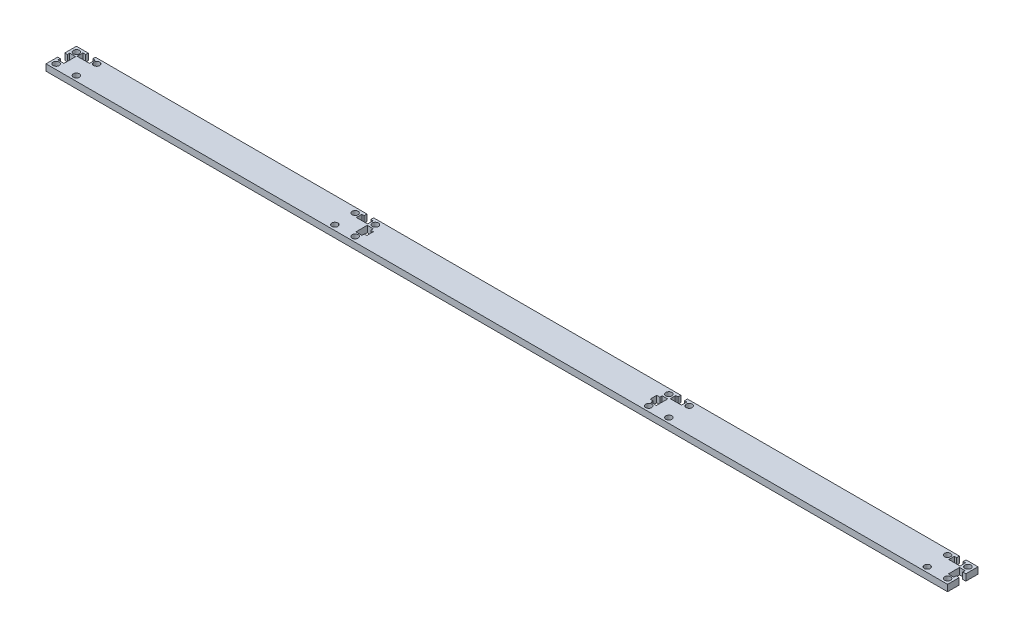
SolidWorks part; units mm, degrees
ref_plane "Front Plane" through (0, 0, 0) normal (0, 0, 1) x (1, 0, 0)
ref_plane "Top Plane" through (0, 0, 0) normal (0, 1, 0) x (1, 0, 0)
ref_plane "Right Plane" through (0, 0, 0) normal (1, 0, 0) x (0, 0, -1)
sketch "Sketch1" plane through (0, 0, 0) normal (0, 1, 0) x (1, 0, 0)
  line L0 (152.4, 7.5) -> (144.9, 7.5)
  line L1 (0, 0) -> (152.4, 0)
  line L2 (0, 0) -> (0, 15)
  line L3 (0, 15) -> (152.4, 15)
  line L4 (152.4, 0) -> (152.4, 15)
  line L5 (0, 7.5) -> (7.5, 7.5)
  line L6 (7.5, 7.5) -> (7.5, 12.5)
  line L7 (7.5, 12.5) -> (2.5, 12.5)
  line L8 (7.5, 12.5) -> (12.5, 12.5)
  line L9 (7.5, 7.5) -> (7.5, 2.5)
  line L10 (7.5, 2.5) -> (2.5, 2.5)
  line L11 (7.5, 2.5) -> (12.5, 2.5)
  line L12 (76.2, 0) -> (76.2, 15)
  line L13 (152.4, 0) -> (152.4, 15)
  line L14 (152.4, 0) -> (292.1, 0)
  line L15 (152.4, 15) -> (292.1, 15)
  line L16 (222.25, 0) -> (222.25, 15)
  line L17 (292.1, 0) -> (292.1, 15)
  line L18 (444.5, 15) -> (292.1, 15)
  line L19 (292.1, 0) -> (292.1, 15)
  line L20 (444.5, 0) -> (292.1, 0)
  line L21 (444.5, 0) -> (444.5, 15)
  circle A0 centre (2.5, 2.5) radius 1.5
  circle A1 centre (2.5, 12.5) radius 1.5
  circle A2 centre (12.5, 12.5) radius 1.5
  circle A3 centre (12.5, 2.5) radius 1.5
  circle A4 centre (149.9, 12.5) radius 1.5
  circle A5 centre (139.9, 12.5) radius 1.5
  circle A6 centre (149.9, 2.5) radius 1.5
  circle A7 centre (139.9, 2.5) radius 1.5
  circle A8 centre (432, 12.5) radius 1.5
  circle A9 centre (442, 12.5) radius 1.5
  circle A10 centre (442, 2.5) radius 1.5
  circle A11 centre (432, 2.5) radius 1.5
  circle A12 centre (294.6, 12.5) radius 1.5
  circle A13 centre (304.6, 12.5) radius 1.5
  circle A14 centre (304.6, 2.5) radius 1.5
  circle A15 centre (294.6, 2.5) radius 1.5
  dimension "D11" = 69.85
  dimension "D1" = 15
  dimension "D2" = 152.4
  dimension "D3" = 7.5
  dimension "D4" = 7.5
  dimension "D5" = 5
  dimension "D6" = 5
  dimension "D7" = 5
  dimension "D8" = 5
  dimension "D9" = 5
  dimension "D10" = 5
extrude "Boss-Extrude1" add sketch "Sketch1" along normal blind 3.175 contours A3 A0 L2 L1 L12 L3 A1 A2 | L12 L1 L4 L3 A6 A4 A5 A7 | L14 L16 L15 L4 | L14 L17 L15 L16 | L20 L21 L18 L17 A15 A14 A13 A12 A10 A8 A9 A11 region at (38.8762, 0, -7.5) region at (113.5238, 0, -7.5) region at (187.325, 0, -7.5) region at (257.175, 0, -7.5) region at (368.3, 0, -7.5)
sketch "Sketch4" plane through (0, 3.175, 0) normal (0, 1, 0) x (1, 0, 0)
  line L0 (444.5, 7.5) -> (432.4339, 7.5)
  line L1 (444.5, 0) -> (444.5, 15) construction
  line L2 (0, 15) -> (444.5, 15) construction
  line L3 (222.25, 15) -> (222.25, 0)
  line L4 (0, 0) -> (444.5, 0) construction
  line L5 (444.5, 9) -> (442.2, 9)
  line L6 (442.2, 9) -> (442.2, 10.15)
  line L7 (442.2, 10.15) -> (440.5, 10.15)
  line L8 (440.5, 10.15) -> (440.5, 7.5)
  line L9 (444.5, 9.25) -> (442.45, 9.25)
  line L10 (442.45, 9.25) -> (442.45, 10.4)
  line L11 (442.45, 10.4) -> (440.25, 10.4)
  line L12 (440.25, 10.4) -> (440.25, 7.5)
  line L13 (444.5, 5.75) -> (442.45, 5.75)
  line L14 (442.45, 5.75) -> (442.45, 4.6)
  line L15 (442.45, 4.6) -> (440.25, 4.6)
  line L16 (440.25, 4.6) -> (440.25, 7.5)
  line L17 (0, 9.25) -> (2.05, 9.25)
  line L18 (2.05, 9.25) -> (2.05, 10.4)
  line L19 (0, 5.75) -> (2.05, 5.75)
  line L20 (2.05, 5.75) -> (2.05, 4.6)
  line L21 (2.05, 4.6) -> (4.25, 4.6)
  line L22 (4.25, 4.6) -> (4.25, 7.5)
  line L23 (4.25, 10.4) -> (4.25, 7.5)
  line L24 (2.05, 10.4) -> (4.25, 10.4)
  line L25 (0, 9.25) -> (0, 5.75)
  line L26 (444.5, 9.25) -> (444.5, 5.75)
  line M20 (0, 15) -> (0, 0)
  line M22 (444.5, 0) -> (444.5, 15)
  dimension "D1" = 1.5
  dimension "D2" = 1.15
  dimension "D3" = 1.7
  dimension "D4" = 2.65
  dimension "D5" = 2.3
  dimension "D6" = 0.25
extrude "Cut-Extrude2" cut sketch "Sketch4" against normal blind 10 contours L16 L15 L14 L13 L0 M22 | L7 L8 L0 L5 L6 M22 | L24 L18 L17 L19 L20 L21 L22 L23 M20 region at (442.1148, 3.175, -6.257) region at (442.2174, 3.175, -8.5756) region at (2.3852, 3.175, -7.5)
sketch "Sketch6" plane through (440.5, 0, 0) normal (1, 0, 0) x (0, 0, -1)
  line L0 (10.15, 0) -> (7.5, 0) construction
  line L5 (7.5, 3.175) -> (10.15, 3.175)
  line L6 (7.5, 3.175) -> (7.5, 0)
  line L7 (7.5, 0) -> (10.15, 0)
  line L8 (10.15, 3.175) -> (10.15, 0)
extrude "Cut-Extrude3" cut sketch "Sketch6" against normal blind 0.25
sketch "Sketch7" plane through (0, 3.175, 0) normal (0, 1, 0) x (1, 0, 0)
  line L0 (440.25, 4.6) -> (440.25, 10.15)
  line L1 (440.25, 10.15) -> (442.2, 10.15)
  line L2 (442.2, 10.15) -> (442.2, 9)
  line L3 (442.2, 9) -> (444.5, 9)
  line L4 (444.5, 9) -> (444.5, 5.75)
  line L5 (444.5, 5.75) -> (442.45, 5.75)
  line L6 (444.5, 5.75) -> (442.45, 5.75) construction
  line L7 (442.45, 5.75) -> (442.45, 4.6)
  line L8 (442.45, 5.75) -> (442.45, 4.6) construction
  line L9 (442.45, 4.6) -> (440.25, 4.6) construction
  line L10 (442.45, 4.6) -> (440.25, 4.6)
  line L11 (368.3, 15) -> (368.3, 0)
  line L12 (0, 15) -> (444.5, 15) construction
  line L13 (0, 0) -> (444.5, 0) construction
  line L30 (439.75, 13.1) -> (439.75, 10.9)
  line L31 (439.75, 10.9) -> (434.2, 10.9)
  line L32 (434.2, 10.9) -> (434.2, 12.85)
  line L33 (434.2, 12.85) -> (435.35, 12.85)
  line L34 (435.35, 12.85) -> (435.35, 15.15)
  line L35 (435.35, 15.15) -> (438.6, 15.15)
  line L36 (438.6, 15.15) -> (438.6, 13.1)
  line L37 (438.6, 13.1) -> (439.75, 13.1)
  line L38 (431.25, 10.4) -> (433.45, 10.4) [skipped]
  line L39 (433.45, 10.4) -> (433.45, 4.85) [skipped]
  line L40 (433.45, 4.85) -> (431.5, 4.85) [skipped]
  line L41 (431.5, 4.85) -> (431.5, 6) [skipped]
  line L42 (431.5, 6) -> (429.2, 6) [skipped]
  line L43 (429.2, 6) -> (429.2, 9.25) [skipped]
  line L44 (429.2, 9.25) -> (431.25, 9.25) [skipped]
  line L45 (431.25, 9.25) -> (431.25, 10.4) [skipped]
  line L46 (433.95, 1.9) -> (433.95, 4.1) [skipped]
  line L47 (433.95, 4.1) -> (439.5, 4.1) [skipped]
  line L48 (439.5, 4.1) -> (439.5, 2.15) [skipped]
  line L49 (439.5, 2.15) -> (438.35, 2.15) [skipped]
  line L50 (438.35, 2.15) -> (438.35, -0.15) [skipped]
  line L51 (438.35, -0.15) -> (435.1, -0.15) [skipped]
  line L52 (435.1, -0.15) -> (435.1, 1.9) [skipped]
  line L53 (435.1, 1.9) -> (433.95, 1.9) [skipped]
  line L54 (298, 13.1) -> (296.85, 13.1)
  line L55 (298, 15.15) -> (298, 13.1)
  line L56 (301.25, 15.15) -> (298, 15.15)
  line L57 (301.25, 12.85) -> (301.25, 15.15)
  line L58 (302.4, 12.85) -> (301.25, 12.85)
  line L59 (302.4, 10.9) -> (302.4, 12.85)
  line L60 (296.85, 10.9) -> (302.4, 10.9)
  line L61 (296.85, 13.1) -> (296.85, 10.9)
  line L62 (294.15, 4.6) -> (296.35, 4.6)
  line L63 (294.15, 5.75) -> (294.15, 4.6)
  line L64 (292.1, 5.75) -> (294.15, 5.75)
  line L65 (292.1, 9) -> (292.1, 5.75)
  line L66 (294.4, 9) -> (292.1, 9)
  line L67 (294.4, 10.15) -> (294.4, 9)
  line L68 (296.35, 10.15) -> (294.4, 10.15)
  line L69 (296.35, 4.6) -> (296.35, 10.15)
  line L70 (222.25, 15) -> (222.25, -3.2604)
  line L71 (148.15, 4.6) -> (148.15, 10.15)
  line L72 (148.15, 10.15) -> (150.1, 10.15)
  line L73 (150.1, 10.15) -> (150.1, 9)
  line L74 (150.1, 9) -> (152.4, 9)
  line L75 (152.4, 9) -> (152.4, 5.75)
  line L76 (152.4, 5.75) -> (150.35, 5.75)
  line L77 (150.35, 5.75) -> (150.35, 4.6)
  line L78 (150.35, 4.6) -> (148.15, 4.6)
  line L79 (147.65, 13.1) -> (147.65, 10.9)
  line L80 (147.65, 10.9) -> (142.1, 10.9)
  line L81 (142.1, 10.9) -> (142.1, 12.85)
  line L82 (142.1, 12.85) -> (143.25, 12.85)
  line L83 (143.25, 12.85) -> (143.25, 15.15)
  line L84 (143.25, 15.15) -> (146.5, 15.15)
  line L85 (146.5, 15.15) -> (146.5, 13.1)
  line L86 (146.5, 13.1) -> (147.65, 13.1)
  circle A0 centre (294.6, 12.5) radius 1.5 construction
  line M51 (440.25, 4.6) -> (440.25, 10.15)
  line M52 (440.25, 10.15) -> (442.2, 10.15)
  line M53 (442.2, 10.15) -> (442.2, 9)
  line M54 (442.2, 9) -> (444.5, 9)
  line M56 (444.5, 15) -> (0, 15)
  line M68 (444.5, 5.75) -> (442.45, 5.75)
  line M69 (442.45, 5.75) -> (442.45, 4.6)
  line M70 (442.45, 4.6) -> (440.25, 4.6)
  dimension "D1" = 73.7
  dimension "D2" = 4
extrude "Cut-Extrude4" cut sketch "Sketch7" against normal blind 10 contours L78 L77 L76 L75 L74 L73 L72 L71 | L86 L85 L83 L82 L81 L80 L79 M56 | L62 L69 L68 L67 L66 L65 L64 L63 | L54 L61 L60 L59 L58 L57 L55 M56 | L37 L36 L34 L33 L32 L31 L30 M56 | L4 M54 M53 M52 M51 M70 M69 M68 region at (442.0967, 3.175, -7.341) region at (144.9099, 3.175, -12.684) region at (299.5901, 3.175, -12.684) region at (437.0099, 3.175, -12.684) region at (294.5033, 3.175, -7.341) region at (149.9967, 3.175, -7.341)
sketch "Sketch10" plane through (2.05, 0, 0) normal (1, 0, 0) x (0, 0, -1)
  line L0 (9.25, 0) -> (10.4, 0) construction
  line L1 (4.6, 3.175) -> (10.4, 3.175)
  line L2 (4.6, 3.175) -> (4.6, 0)
  line L3 (4.6, 0) -> (10.4, 0)
  line L4 (10.4, 3.175) -> (10.4, 0)
extrude "Cut-Extrude5" cut sketch "Sketch10" against normal blind 0.762
sketch "Sketch11" plane through (150.35, 0, 0) normal (-1, 0, 0) x (0, 0, 1)
  line L5 (-4.6, 3.175) -> (-10.2429, 3.175)
  line L6 (-4.6, 3.175) -> (-4.6, -0.5973)
  line L7 (-4.6, -0.5973) -> (-10.2429, -0.5973)
  line L8 (-10.2429, 3.175) -> (-10.2429, -0.5973)
extrude "Cut-Extrude8" cut sketch "Sketch11" against normal blind 0.762 contours L5 L8 L7 L6
sketch "Sketch13" plane through (0, 3.175, 0) normal (0, 1, 0) x (1, 0, 0)
  line L0 (148.15, 4.6) -> (148.15, 10.15) construction
  line L1 (151.112, 10.2429) -> (148.15, 10.2429)
  line L2 (151.112, 10.2429) -> (151.112, 9.9736)
  line L3 (151.112, 9.9736) -> (148.15, 9.9736)
  line L4 (148.15, 10.2429) -> (148.15, 9.9736)
  line L6 (149.0185, 9.9736) -> (150.5694, 9.9736)
  line L7 (149.0185, 9.9736) -> (149.0185, 8.9396)
  line L8 (149.0185, 8.9396) -> (150.5694, 8.9396)
  line L9 (150.5694, 9.9736) -> (150.5694, 8.9396)
extrude "Cut-Extrude10" cut sketch "Sketch13" against normal blind 40.762 contours L1 L4 L3 L2 | L9 L3 L7 L8 region at (149.631, 3.175, -10.1083) region at (149.794, 3.175, -9.4566)
sketch "Sketch16" plane through (0, 3.175, 0) normal (0, 1, 0) x (1, 0, 0)
  line L1 (142.1, 12.85) -> (147.6686, 12.85)
  line L2 (142.1, 12.85) -> (142.1, 13.612)
  line L3 (142.1, 13.612) -> (147.6686, 13.612)
  line L4 (147.6686, 12.85) -> (147.6686, 13.612)
  dimension "D1" = 0.762
extrude "Cut-Extrude12" cut sketch "Sketch16" against normal blind 10.762
sketch "Sketch17" plane through (0, 3.175, 0) normal (0, 1, 0) x (1, 0, 0)
  line L1 (294.4, 10.15) -> (293.638, 10.15)
  line L2 (294.4, 10.15) -> (294.4, 4.5861)
  line L3 (294.4, 4.5861) -> (293.638, 4.5861)
  line L4 (293.638, 10.15) -> (293.638, 4.5861)
  dimension "D1" = 0.762
extrude "Cut-Extrude13" cut sketch "Sketch17" against normal blind 10.762
sketch "Sketch18" plane through (0, 3.175, 0) normal (0, 1, 0) x (1, 0, 0)
  line L5 (302.4, 12.85) -> (296.8744, 12.85)
  line L6 (302.4, 12.85) -> (302.4, 13.612)
  line L7 (302.4, 13.612) -> (296.8744, 13.612)
  line L8 (296.8744, 12.85) -> (296.8744, 13.612)
  dimension "D1" = 0.762
extrude "Cut-Extrude14" cut sketch "Sketch18" against normal blind 10.762
sketch "Sketch19" plane through (0, 3.175, 0) normal (0, 1, 0) x (1, 0, 0)
  line L1 (442.2, 10.15) -> (442.962, 10.15)
  line L2 (442.2, 10.15) -> (442.2, 4.6219)
  line L3 (442.2, 4.6219) -> (442.962, 4.6219)
  line L4 (442.962, 10.15) -> (442.962, 4.6219)
  dimension "D1" = 0.762
extrude "Cut-Extrude15" cut sketch "Sketch19" against normal blind 10.762
sketch "Sketch20" plane through (0, 3.175, 0) normal (0, 1, 0) x (1, 0, 0)
  line L1 (434.2, 12.85) -> (439.726, 12.85)
  line L2 (434.2, 12.85) -> (434.2, 13.612)
  line L3 (434.2, 13.612) -> (439.726, 13.612)
  line L4 (439.726, 12.85) -> (439.726, 13.612)
  dimension "D1" = 0.762
extrude "Cut-Extrude16" cut sketch "Sketch20" against normal blind 10.762
sketch "Sketch21" plane through (0, 3.175, 0) normal (0, 1, 0) x (1, 0, 0)
  line L0 (7.62, 15) -> (7.62, -0.5799)
  line L1 (0, 15) -> (143.25, 15) construction
  line L2 (0, 9.25) -> (0, 15) construction
  line L3 (9.398, 15) -> (9.398, 13.73)
  line L8 (9.398, 15) -> (5.842, 15)
  line L9 (7.62, 15) -> (7.62, 13.73)
  line L10 (9.398, 13.73) -> (5.842, 13.73)
  line L11 (5.842, 15) -> (5.842, 13.73)
  dimension "D1" = 7.62
  dimension "D2" = 1.778
  dimension "D3" = 1.27
extrude "Cut-Extrude17" cut sketch "Sketch21" against normal blind 10.762 contours L8 L11 L10 L0 | L10 L11 L8 L3 region at (6.731, 3.175, -14.365)
sketch "Sketch22" plane through (0, 3.175, 0) normal (0, 1, 0) x (1, 0, 0)
  line L1 (4.4006, 13.73) -> (10.5207, 13.73)
  line L2 (4.4006, 13.73) -> (4.4006, 10.8904)
  line L3 (4.4006, 10.8904) -> (10.5207, 10.8904)
  line L4 (10.5207, 13.73) -> (10.5207, 10.8904)
extrude "Cut-Extrude18" cut sketch "Sketch22" against normal blind 10
